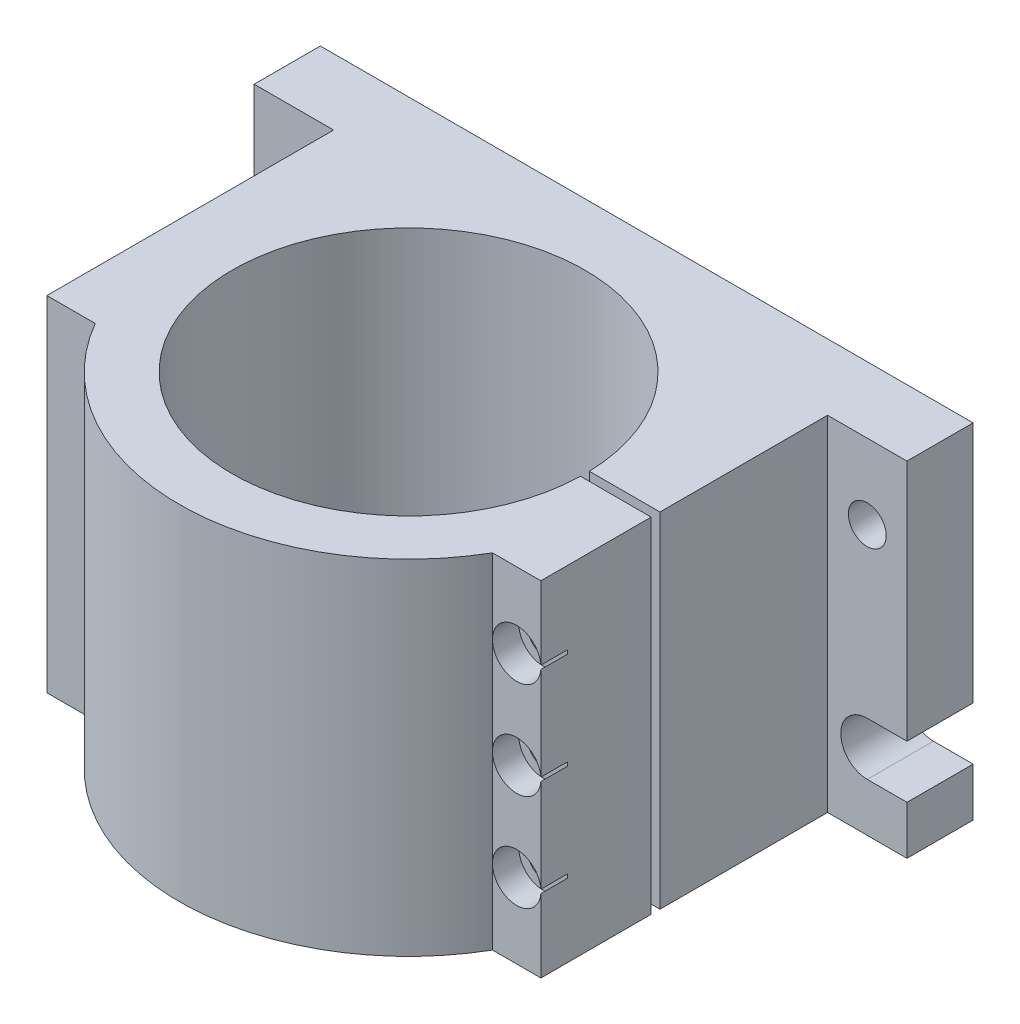
SolidWorks part; units mm, degrees
material "AA356.0-F"
ref_plane "Front Plane" through (0, 0, 0) normal (0, 0, 1) x (1, 0, 0)
ref_plane "Top Plane" through (0, 0, 0) normal (0, 1, 0) x (1, 0, 0)
ref_plane "Right Plane" through (0, 0, 0) normal (1, 0, 0) x (0, 0, -1)
sketch "Sketch1" plane through (0, 0, 0) normal (0, 1, 0) x (1, 0, 0)
  line L0 (-74, 54) -> (74, 54)
  line L1 (74, 54) -> (74, 39)
  line L2 (74, 39) -> (56, 39)
  line L3 (56, 39) -> (56, -26)
  line L4 (56, -26) -> (45.0333, -26)
  line L5 (-74, 54) -> (-74, 39)
  line L6 (-74, 39) -> (-56, 39)
  line L7 (-56, 39) -> (-56, -26)
  line L8 (-56, -26) -> (-45.0333, -26)
  circle A0 centre (0, 0) radius 40
  arc A1 (45.0333, -26) -> (-45.0333, -26) centre (0, 0) cw
  point P12 (0, 0)
  dimension "D1" = 80
  dimension "D2" = 148
  dimension "D3" = 106
  dimension "D4" = 54
  dimension "D5" = 18
  dimension "D6" = 65
  dimension "D7" = 15
extrude "Boss-Extrude1" add sketch "Sketch1" along normal mid plane 78
sketch "Sketch2" plane through (0, 0, 0) normal (0, 1, 0) x (1, 0, 0)
  line L0 (56, -26) -> (56, 39) construction
  line L1 (0, 1) -> (56, 1)
  line L2 (0, 1) -> (0, -1)
  line L3 (0, -1) -> (56, -1)
  line L4 (56, 1) -> (56, -1)
  dimension "D1" = 2
extrude "Cut-Extrude1" cut sketch "Sketch2" against normal up to next and the other way up to next
hole_wizard "CBORE for M6 SHCS1" positions "Sketch3" profile "Sketch4" counterbore size "M6" standard "ANSI Metric" end condition up to next
sketch "Sketch3" plane through (0, 0, 26) normal (0, 0, 1) x (1, 0, 0)
  line L0 (50.5167, 22) -> (50.5167, 0)
  line L1 (50.5167, 0) -> (50.5167, -22)
  line L3 (58.3, 0) -> (-58.3, 0) construction
  line L4 (45.0333, -39) -> (56, -39) construction
  point P1 (50.5167, 22)
  point P2 (50.5167, 0)
  point P3 (50.5167, -22)
  point P10 (50.5167, -39)
  dimension "D1" = 22
sketch "Sketch4" plane through (50.5167, 22, 26) normal (1, 0, 0) x (0, -1, 0)
  line L0 (0, 0) -> (0, 25)
  line L1 (0, 25) -> (3.3, 25)
  line L3 (3.3, 25) -> (3.3, 6)
  line L4 (3.3, 6) -> (5.5, 6)
  line L5 (5.5, 6) -> (5.5, 0)
  line L7 (5.5, 0) -> (0, 0)
  line L11 (0, -6.35) -> (0, 107.95) construction
  dimension "Thru Hole Dia." = 6.6
  dimension "Thru Hole Depth" = 25
  dimension "C'Bore Dia." = 11
  dimension "C'Bore Depth" = 6
sketch "Sketch5" plane through (0, 0, -39) normal (0, 0, 1) x (1, 0, 0)
  line L0 (65, -16) -> (74, -16)
  line L1 (65, 22) -> (-65, 22) construction
  line L2 (65, 22) -> (65, -22) construction
  line L3 (65, -22) -> (-65, -22) construction
  line L4 (-65, 22) -> (-65, -22) construction
  line L5 (65, 22) -> (-65, -22) construction
  line L6 (65, -22) -> (-65, 22) construction
  line L7 (74, 39) -> (74, -39) construction
  line L8 (74, -16) -> (74, -28)
  line L9 (74, -28) -> (65, -28)
  circle A0 centre (65, 22) radius 4.3
  circle A1 centre (-65, -22) radius 4.3
  circle A2 centre (-65, 22) radius 5.05
  arc A3 (65, -16) -> (65, -28) centre (65, -22) ccw
  point P0 (0, 0)
  dimension "D4" = 8.6
  dimension "D5" = 10.1
  dimension "D1" = 44
  dimension "D2" = 130
  dimension "D3" = 12
extrude "Cut-Extrude2" cut sketch "Sketch5" against normal up to next
